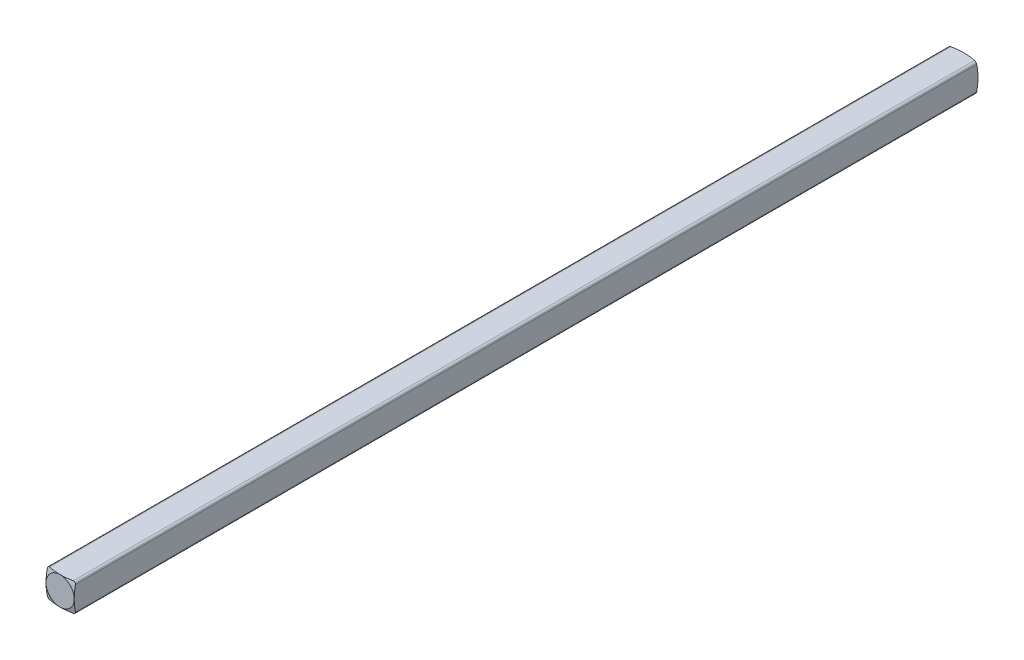
SolidWorks part; units mm, degrees
material "Plain Carbon Steel"
ref_plane "Front Plane" through (0, 0, 0) normal (0, 0, 1) x (1, 0, 0)
ref_plane "Top Plane" through (0, 0, 0) normal (0, 1, 0) x (1, 0, 0)
ref_plane "Right Plane" through (0, 0, 0) normal (1, 0, 0) x (0, 0, -1)
sketch "Sketch1" plane through (0, 0, 0) normal (0, 0, 1) x (1, 0, 0)
  line L0 (0.0501, 1.585) -> (0.0501, -1.585) construction
  line L1 (-1.5349, -1.585) -> (1.6351, -1.585)
  line L2 (-1.5349, -1.585) -> (-1.5349, 1.585)
  line L3 (-1.5349, 1.585) -> (1.6351, 1.585)
  line L4 (1.6351, -1.585) -> (1.6351, 1.585)
  line L5 (1.6351, 0) -> (-1.5349, 0) construction
  dimension "D1" = 3.17
  dimension "D2" = 3.17
  dimension "D3" = 1.6351
extrude "Extrude1" add sketch "Sketch1" along normal mid plane 101.6
sketch "Sketch4" plane through (0, 0, 0) normal (0, -1, 0) x (1, 0, 0)
  line L0 (1.6351, 50.8) -> (2.5551, 50.8)
  line L2 (2.5551, 50.8) -> (2.5551, 50.53)
  line L5 (0.0501, -50.8) -> (0.0501, 2.4929) construction
  line L6 (-1.5349, -50.8) -> (1.6351, -50.8) construction
  line L7 (1.6351, 11.0508) -> (1.6351, 10.1958) construction
  line L8 (2.5551, 50.53) -> (1.6351, 50.8)
  dimension "D1" = 0.27
  dimension "D2" = 0.9588
revolve "Cut-Revolve3" cut sketch "Sketch4" angle 360 about L5
mirror "Mirror2" about plane through (0, 0, 0) normal (0, 0, 1) of "Cut-Revolve3"
fillet "Fillet1" radius 0.25 4 edges at (1.6351, 1.585, 0) (1.6351, -1.585, 0) (-1.5349, -1.585, 0) (-1.5349, 1.585, 0)
ref_axis "Axis1" through (0.0501, 0, 29.118) along (0, 0, -1)
ref_plane "Plane1" through (0, 0, 14.53) normal (0, 0, 1) x (1, 0, 0)
ref_plane "Plane2" through (0, 0, 22.05) normal (0, 0, 1) x (1, 0, 0)
ref_plane "Plane3" through (0, 0, 8.06) normal (0, 0, -1) x (-1, 0, 0)
ref_plane "Plane4" through (0, 0, 39.38) normal (0, 0, 1) x (1, 0, 0)
ref_plane "Plane5" through (0, 0, -32.46) normal (0, 0, -1) x (-1, 0, 0)
ref_plane "Plane6" through (0, 0, 31.76) normal (0, 0, 1) x (1, 0, 0)
ref_plane "Plane7" through (0, 0, -9.8) normal (0, 0, -1) x (-1, 0, 0)
ref_plane "Plane8" through (0, 0, -42.2) normal (0, 0, -1) x (-1, 0, 0)
ref_plane "Plane9" through (0, 0, -5.8) normal (0, 0, -1) x (-1, 0, 0)
ref_plane "Plane10" through (0, 0, 2.9) normal (0, 0, -1) x (-1, 0, 0)
